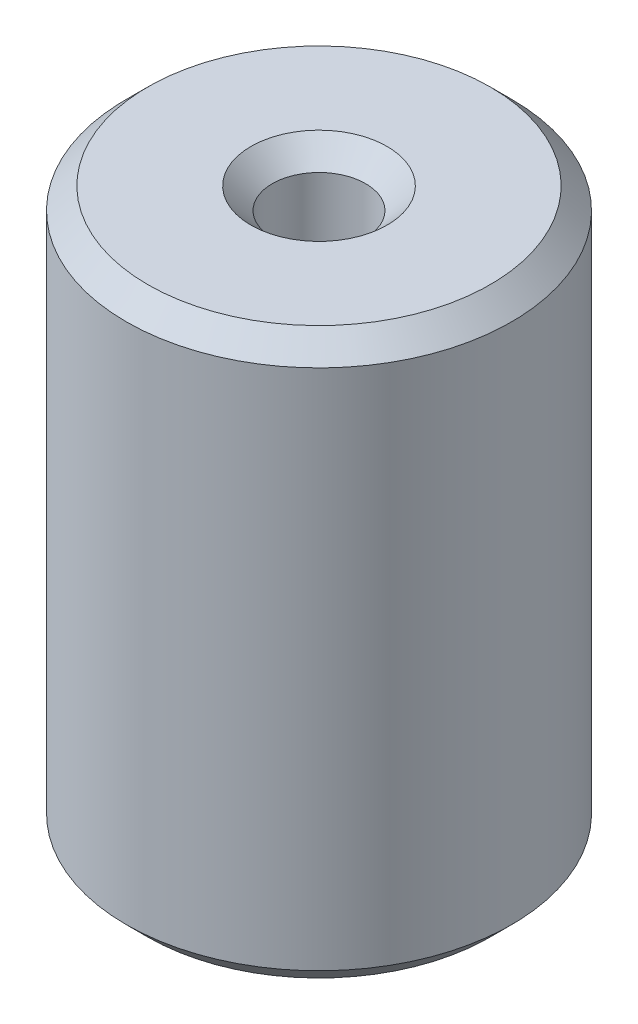
SolidWorks part; units mm, degrees
ref_plane "Front Plane" through (0, 0, 0) normal (0, 0, 1) x (1, 0, 0)
ref_plane "Top Plane" through (0, 0, 0) normal (0, 1, 0) x (1, 0, 0)
ref_plane "Right Plane" through (0, 0, 0) normal (1, 0, 0) x (0, 0, -1)
sketch "Sketch1" plane through (0, 0, 0) normal (0, 1, 0) x (1, 0, 0)
  circle A0 centre (0, 0) radius 5
  dimension "SLEEVE_OD" = 10
extrude "Boss-Extrude1" add sketch "Sketch1" along normal blind 14.6604
sketch "Sketch2" plane through (0, 0, 0) normal (0, 1, 0) x (1, 0, 0)
  circle A0 centre (0, 0) radius 1.2113
  dimension "BORE_D" = 2.4226
extrude "Cut-Extrude1" cut sketch "Sketch2" along normal through all
chamfer "Chamfer1" distance 0.5571 angle 45 4 edges at (0, 14.6604, 1.2113) (0, 0, 1.2113) (0, 0, 5) (0, 14.6604, 5)
